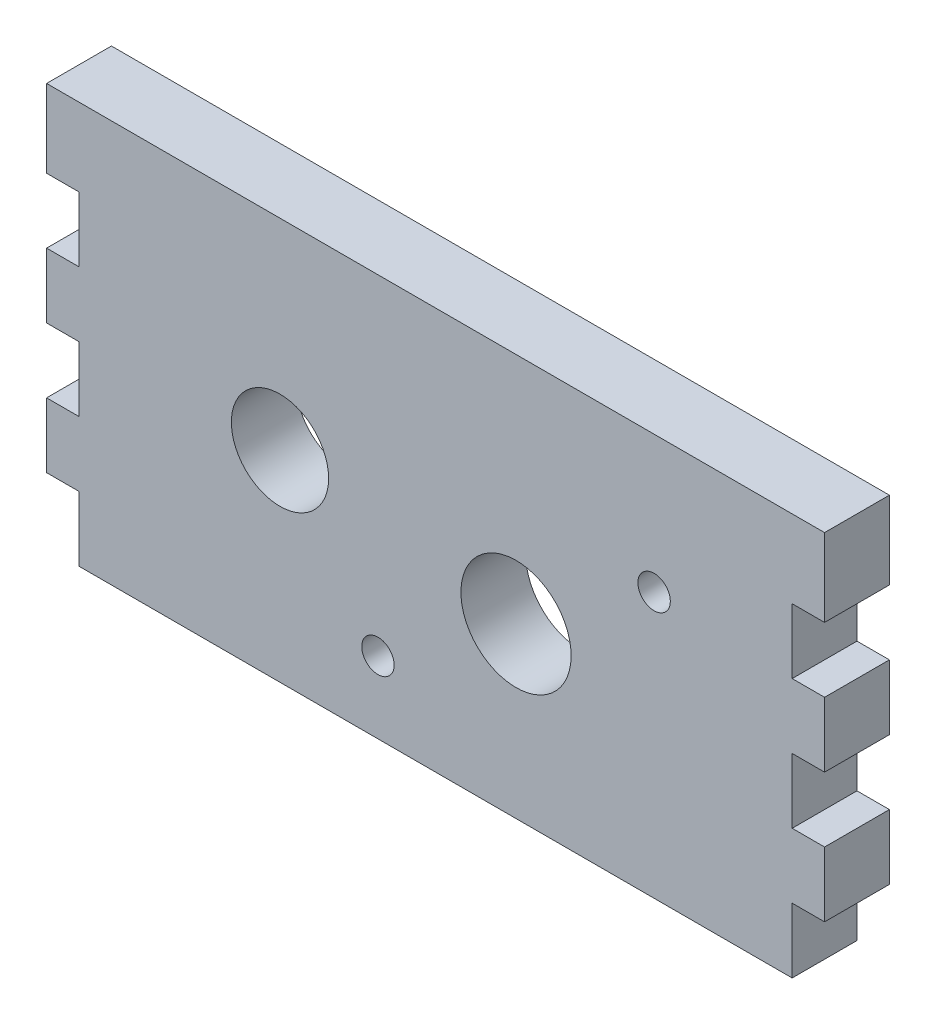
SolidWorks part; units mm, degrees
ref_plane "정면" through (0, 0, 0) normal (0, 0, 1) x (1, 0, 0)
ref_plane "윗면" through (0, 0, 0) normal (0, 1, 0) x (1, 0, 0)
ref_plane "우측면" through (0, 0, 0) normal (1, 0, 0) x (0, 0, -1)
sketch "스케치2" plane through (0, 0, 0) normal (0, 0, 1) x (1, 0, 0)
  line L0 (-6.0717, -5) -> (65.5766, -5) construction
  line L1 (-60, -31) -> (60, -31)
  line L2 (-60, -31) -> (-60, 31)
  line L3 (-60, 31) -> (60, 31)
  line L4 (60, -31) -> (60, 31)
  line L5 (-60, -31) -> (60, 31) construction
  line L6 (-60, 31) -> (60, -31) construction
  line L7 (-15.8273, -24.7708) -> (37.7136, 12.7189) construction
  circle A0 centre (12.4083, -5) radius 8.5
  circle A1 centre (-24, 0) radius 7.5
  circle A2 centre (33.7062, 9.913) radius 2.5
  circle A3 centre (-8.8897, -19.913) radius 2.5
  point P0 (0, 0)
  dimension "D5" = 17
  dimension "D8" = 15
  dimension "D9" = 35
  dimension "D10" = 5
  dimension "D1" = 62
  dimension "D2" = 120
  dimension "D3" = 36.75
  dimension "D4" = 36
  dimension "D6" = 31
  dimension "D7" = 36
  dimension "D11" = 26
  dimension "D12" = 26
extrude "보스-돌출1" add sketch "스케치2" along normal blind 10 contours L1 L4 L3 L2 A1 A0 region at (0.134, 0.1903, 0)
sketch "스케치3" plane through (0, 0, 10) normal (0, 0, 1) x (1, 0, 0)
  line L0 (-60, -31) -> (-60, 31) construction
  line L1 (-60, -21) -> (-55, -21)
  line L2 (-60, -21) -> (-60, -31)
  line L3 (-60, -31) -> (-55, -31)
  line L4 (-55, -21) -> (-55, -31)
  line L5 (-60, -31) -> (60, -31) construction
  dimension "D1" = 5
  dimension "D2" = 10
extrude "컷-돌출1" cut sketch "스케치3" against normal up to next
pattern_linear "선형 패턴1" count 3 spacing 20 along (0, 1, 0) of "컷-돌출1"
mirror "대칭 복사1" about plane through (0, 0, 0) normal (1, 0, 0) of "선형 패턴1"
